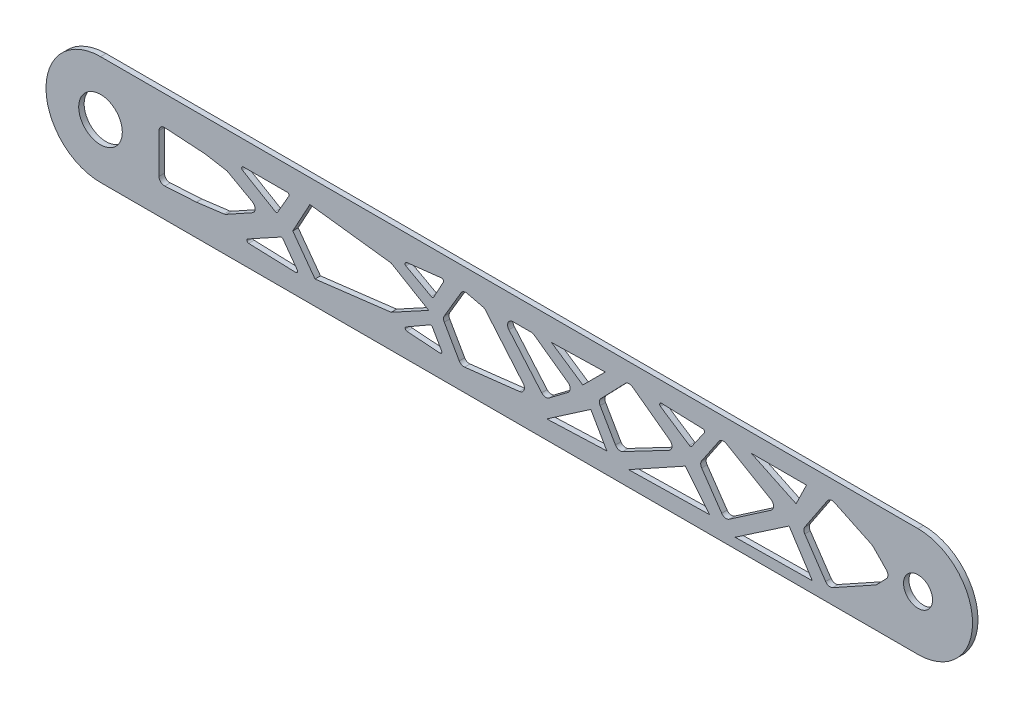
SolidWorks part; units mm, degrees
material "6061-T6 (SS)"
ref_plane "Front Plane" through (0, 0, 0) normal (0, 0, 1) x (1, 0, 0)
ref_plane "Top Plane" through (0, 0, 0) normal (0, 1, 0) x (1, 0, 0)
ref_plane "Right Plane" through (0, 0, 0) normal (1, 0, 0) x (0, 0, -1)
sketch "Sketch1" plane through (0, 0, 0) normal (0, 0, 1) x (1, 0, 0)
  line L0 (0, 0) -> (450, 0) construction
  line L1 (0, 30) -> (450, 30)
  line L2 (0, -30) -> (450, -30)
  arc A0 (0, 30) -> (0, -30) centre (0, 0) ccw
  arc A1 (450, -30) -> (450, 30) centre (450, 0) ccw
  circle A2 centre (0, 0) radius 12
  circle A9 centre (0, 0) radius 10 construction
  point P3 (225, 0)
  point P24 (0, 0)
  dimension "D1" = 30
  dimension "D3" = 24
  dimension "D6" = 20
  dimension "D2" = 450
extrude "Boss-Extrude1" add sketch "Sketch1" along normal blind 3
sketch "Sketch2" plane through (0, 0, 0) normal (0, 0, -1) x (-1, 0, 0)
  circle A0 centre (-450, 0) radius 8
  dimension "D1" = 16
extrude "Cut-Extrude1" cut sketch "Sketch2" against normal blind 10
sketch "Sketch3" plane through (0, 0, 0) normal (0, 0, -1) x (-1, 0, 0)
  line L0 (-225, 30) -> (-225, -30) construction
  line L1 (-450, 30) -> (0, 30) construction
  line L2 (0, -30) -> (-450, -30) construction
sketch "Sketch4" plane through (0, 0, 3) normal (0, 0, 1) x (1, 0, 0)
  line L3 (75.0512, 16.7519) -> (104.4964, 16.7519)
  line L4 (104.4964, 16.7519) -> (97.0103, 3.776)
  line L5 (97.0103, 3.776) -> (75.0512, 16.7519)
  line L6 (115.2364, 17.1336) -> (159.9949, 11.5901)
  line L7 (159.9949, 11.5901) -> (180.6552, -0.6182)
  line L8 (159.9949, -11.858) -> (118.0851, -16.9668)
  line L9 (118.0851, -16.9668) -> (105.8233, -0.1776)
  line L10 (105.8233, -0.1776) -> (115.2364, 17.1336)
  line L11 (189.6655, 18.5783) -> (182.9411, 6.2118)
  line L12 (189.6655, 18.5783) -> (165.3685, 15.767)
  line L13 (165.3685, 15.767) -> (182.9411, 6.2118)
  line L14 (199.5998, 18.5783) -> (188.3613, -0.4406)
  line L15 (188.3613, -0.4406) -> (198.4445, -18.0218)
  line L16 (198.4445, -18.0218) -> (236.2169, -13.6513)
  line L17 (236.2169, -13.6513) -> (211.3582, 15.767)
  line L18 (211.3582, 15.767) -> (199.5998, 18.5783)
  line L19 (220.5269, 17.1727) -> (237.9604, 17.1727)
  line L20 (237.9604, 17.1727) -> (260.5594, 1.0579)
  line L21 (244.6755, -10.9439) -> (220.5269, 17.1727)
  line L22 (265.4666, 6.2118) -> (277.8331, 18.5783)
  line L23 (277.8331, 18.5783) -> (248.2204, 17.8749)
  line L24 (248.2204, 17.8749) -> (265.4666, 6.2118)
  line L25 (165.3685, -16.3587) -> (182.2005, -6.7053)
  line L26 (182.2005, -6.7053) -> (188.6908, -18.0218)
  line L27 (188.6908, -18.0218) -> (165.3685, -16.3587)
  line L28 (245.6374, -19.8683) -> (269.8878, -3.2204)
  line L29 (269.8878, -3.2204) -> (278.7166, -18.6146)
  line L30 (278.7166, -18.6146) -> (245.6374, -19.8683)
  line L32 (290.6832, -21.5398) -> (321.9406, -4.2114)
  line L33 (321.9406, -4.2114) -> (335.2064, -20.704)
  line L34 (335.2064, -20.704) -> (290.6832, -21.5398)
  line L35 (341.9929, 19.1834) -> (329.7352, 1.0579)
  line L36 (329.7352, 1.0579) -> (343.6146, -19.1598)
  line L37 (343.6146, -19.1598) -> (373.065, 1.0579)
  line L38 (373.065, 1.0579) -> (341.9929, 19.1834)
  line L39 (244.6755, -10.9439) -> (260.5594, 1.0579)
  line L40 (273.8778, 3.1142) -> (290.6832, 20.5427)
  line L41 (290.6832, 20.5427) -> (317.2099, 1.0579)
  line L42 (317.2099, 1.0579) -> (284.8817, -15.8863)
  line L43 (284.8817, -15.8863) -> (273.8778, 3.1142)
  line L44 (305.3074, 19.271) -> (333.3759, 18.3243)
  line L45 (333.3759, 18.3243) -> (324.9421, 6.2118)
  line L46 (324.9421, 6.2118) -> (305.3074, 19.271)
  line L47 (358.198, 20.0502) -> (388.5975, 20.0502)
  line L48 (388.5975, 20.0502) -> (382.8865, 8.2928)
  line L49 (382.8865, 8.2928) -> (358.198, 20.0502)
  line L50 (349.331, -24.4281) -> (379.0302, -4.2114)
  line L51 (379.0302, -4.2114) -> (391.83, -23.927)
  line L52 (391.83, -23.927) -> (349.331, -24.4281)
  line L53 (386.543, -2.0485) -> (401.5864, 20.5696)
  line L54 (401.5864, 20.5696) -> (424.8813, 9.4759)
  line L55 (434.601, -0.4406) -> (424.8813, 9.4759)
  line L56 (434.601, -0.4406) -> (426.9833, -8.3408)
  line L57 (426.9833, -8.3408) -> (400.6645, -22.9126)
  line L58 (400.6645, -22.9126) -> (386.543, -2.0485)
  line L59 (159.9949, -11.858) -> (180.6552, -0.6182)
  line L60 (77.9082, -18.1131) -> (99.9591, -5.986)
  line L61 (99.9591, -5.986) -> (109.5177, -19.2166)
  line L62 (109.5177, -19.2166) -> (77.9082, -18.1131)
  line L63 (32.1814, 14.0452) -> (32.1814, -14.1865)
  line L64 (32.1814, -14.1865) -> (52.8225, -12.9556)
  line L65 (52.8225, -12.9556) -> (68.5544, -10.9439)
  line L66 (68.5544, -10.9439) -> (88.303, 0)
  line L67 (88.303, 0) -> (69.6625, 10.3469)
  line L68 (69.6625, 10.3469) -> (57.5717, 12.4236)
  line L69 (57.5717, 12.4236) -> (32.1814, 14.0452)
extrude "Cut-Extrude2" cut sketch "Sketch4" against normal blind 10
fillet "Fillet1" radius 3 7 edges at (57.5717, 12.4236, 1.5) (69.6625, 10.3469, 1.5) (88.303, 0, 1.5) (52.8225, -12.9556, 1.5) (68.5544, -10.9439, 1.5) (32.1814, -14.1865, 1.5) (32.1814, 14.0452, 1.5)
fillet "Fillet2" radius 1 15 edges at (324.9421, 6.2118, 1.5) (333.3759, 18.3243, 1.5) (305.3074, 19.271, 1.5) (189.6655, 18.5783, 1.5) (182.9411, 6.2118, 1.5) (165.3685, 15.767, 1.5) (182.2005, -6.7053, 1.5) (188.6908, -18.0218, 1.5) (165.3685, -16.3587, 1.5) (109.5177, -19.2166, 1.5) (99.9591, -5.986, 1.5) (77.9082, -18.1131, 1.5) (97.0103, 3.776, 1.5) (104.4964, 16.7519, 1.5) (75.0512, 16.7519, 1.5)
fillet "Fillet3" radius 3 23 edges at (400.6645, -22.9126, 1.5) (401.5864, 20.5696, 1.5) (260.5594, 1.0579, 1.5) (220.5269, 17.1727, 1.5) (244.6755, -10.9439, 1.5) (343.6146, -19.1598, 1.5) (284.8817, -15.8863, 1.5) (317.2099, 1.0579, 1.5) (236.2169, -13.6513, 1.5) (237.9604, 17.1727, 1.5) (211.3582, 15.767, 1.5) (199.5998, 18.5783, 1.5) (341.9929, 19.1834, 1.5) (290.6832, 20.5427, 1.5) (198.4445, -18.0218, 1.5) (188.3613, -0.4406, 1.5) (273.8778, 3.1142, 1.5) (329.7352, 1.0579, 1.5) (386.543, -2.0485, 1.5) (424.8813, 9.4759, 1.5) (426.9833, -8.3408, 1.5) (434.601, -0.4406, 1.5) (373.065, 1.0579, 1.5)
